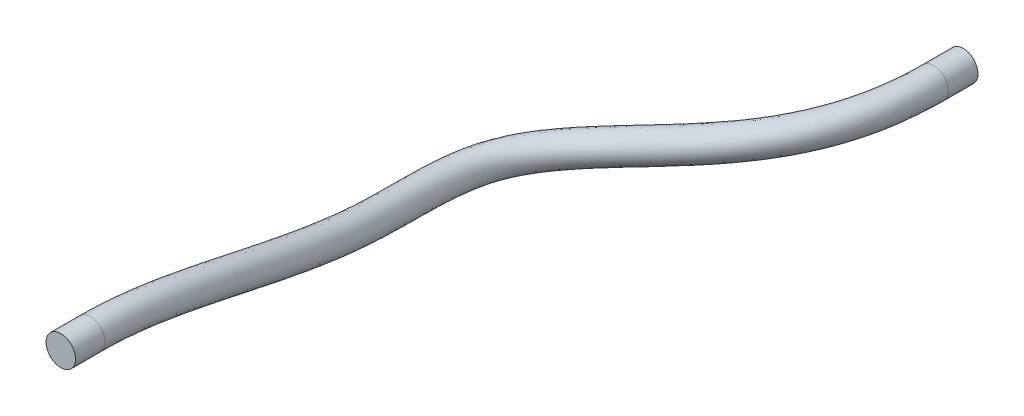
SolidWorks part; units mm, degrees
ref_plane "Front Plane" through (0, 0, 0) normal (0, 0, 1) x (1, 0, 0)
ref_plane "Top Plane" through (0, 0, 0) normal (0, 1, 0) x (1, 0, 0)
ref_plane "Right Plane" through (0, 0, 0) normal (1, 0, 0) x (0, 0, -1)
sketch3d "3DSketch2"
  line L0 (1.5, -2, 0) -> (1.5, -2, 1)
  line L1 (-4.5, -1.1, 24.5) -> (-4.5, -1.1, 23.5)
  circle A0 centre (1.5, -2, 0) radius 0.5 construction
  circle A1 centre (-4.5, -1.1, 24.5) radius 0.5 construction
  spline S0 degree 3 poles (-4.5, -1.1, 23.5) (-4.5, -1.1, 20.5307) (-4.0983, -2.4862, 16.1708) (-5.442, -3.0527, 7.2289) (1.5, -2, 6.589) (1.5, -2, 1) knots 0 0 0 0 0.388012 0.552696 1 1 1 1
  point P4 (1.5, -2, 0.5)
  point P9 (-4.5, -1.1, 24)
  dimension "D4" = 24.9167
  dimension "D5" = 8.908
  dimension "D6" = 16.7671
  dimension "D1" = 2.0174
  dimension "D2" = 2.2913
  dimension "D3" = 10.9337
  dimension "D7" = 9.4844
  dimension "D8" = 4.0255
sweep "Sweep1" add path "3DSketch2" circular profile diameter 1 parameters "D3"=1
